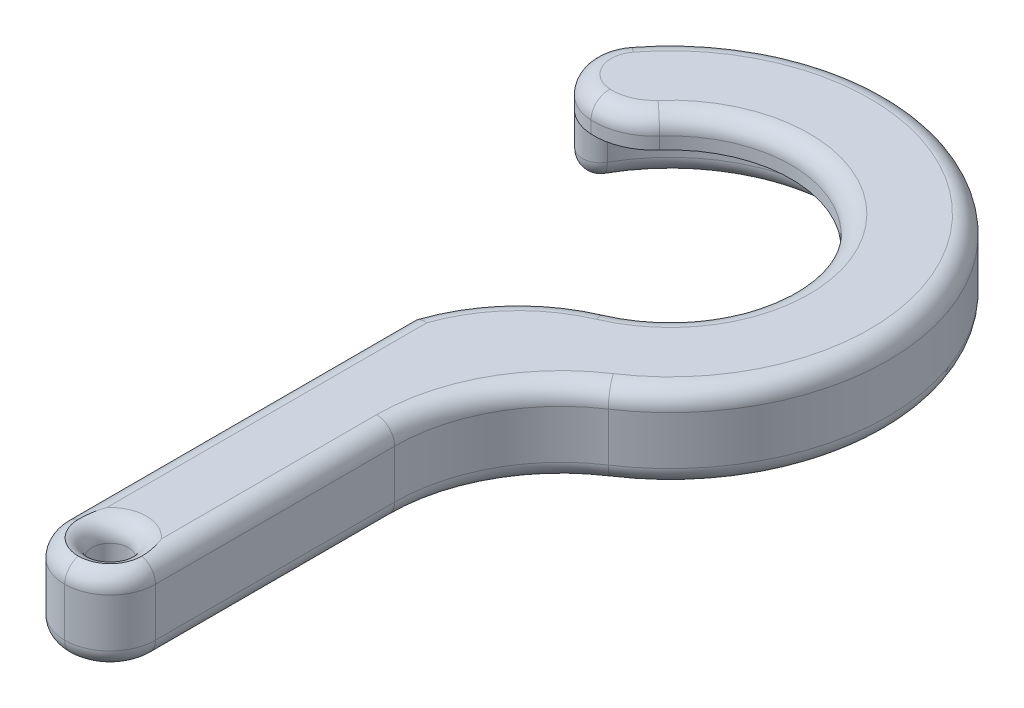
SolidWorks part; units mm, degrees
ref_plane "Front Plane" through (0, 0, 0) normal (0, 0, 1) x (1, 0, 0)
ref_plane "Top Plane" through (0, 0, 0) normal (0, 1, 0) x (1, 0, 0)
ref_plane "Right Plane" through (0, 0, 0) normal (1, 0, 0) x (0, 0, -1)
sketch "Sketch1" plane through (0, 0, 0) normal (0, 1, 0) x (1, 0, 0)
  circle A0 centre (0, 0) radius 6.858
  circle A1 centre (0, 0) radius 9.144
  dimension "D1" = 13.716
  dimension "D2" = 2.286
extrude "Boss-Extrude1" add sketch "Sketch1" along normal blind 2.286
sketch "Sketch2" plane through (0, 2.286, 0) normal (0, 1, 0) x (1, 0, 0)
  circle A0 centre (0, 0) radius 5.08
  circle M1 centre (0, 0) radius 9.144
  circle M2 centre (0, 0) radius 6.858
  dimension "D1" = 10.16
extrude "Boss-Extrude2" add sketch "Sketch2" along normal blind 1.27 contours A0 M2 | M1 M2
sketch "Sketch3" plane through (0, 3.556, 0) normal (0, 1, 0) x (1, 0, 0)
  line L0 (0, -1000) -> (0, 49000) construction
  line L1 (-1.905, -7.62) -> (1.905, -7.62)
  line L2 (-1.905, -7.62) -> (-1.905, -25.4)
  line L3 (-1.905, -25.4) -> (1.905, -25.4)
  line L4 (1.905, -7.62) -> (1.905, -25.4)
  dimension "D1" = 3.81
  dimension "D2" = 7.62
  dimension "D3" = 25.4
extrude "Boss-Extrude3" add sketch "Sketch3" against normal up to surface (3.556 mm away) up to face at (0, 0, 9.144)
sketch "Sketch4" plane through (0, 3.556, 0) normal (0, 1, 0) x (1, 0, 0)
  line L0 (-1.905, -8.9434) -> (0, 0)
  line L1 (0, 0) -> (-8.4767, 3.4291)
  arc A0 (1.905, -8.9434) -> (-1.905, -8.9434) centre (0, 0) ccw construction
  dimension "D1" = 100
extrude "Cut-Extrude1" cut sketch "Sketch4" against normal through all and the other way through all
fillet "Fillet1" radius 1.905 2 edges at (-1.905, 1.778, 25.4) (1.905, 1.778, 25.4)
sketch "Sketch5" plane through (0, 3.556, 0) normal (0, 1, 0) x (1, 0, 0)
  circle A0 centre (0, -23.495) radius 0.762
  arc A1 (-1.905, -23.495) -> (0, -25.4) centre (0, -23.495) ccw construction
  dimension "D1" = 1.524
extrude "Cut-Extrude2" cut sketch "Sketch5" against normal through all
fillet "Fillet2" radius 6.985 1 edges at (1.905, 1.778, 8.9434)
fillet "Fillet3" radius 6.985 1 edges at (-1.0583, 2.921, 4.9685)
fillet "Fillet4" radius 2.54 1 edges at (-4.7093, 2.921, -1.905)
fillet "Fillet5" radius 1.905 1 edges at (-8.4767, 1.778, -3.4291)
fillet "Fillet6" radius 0.762 2 edges at (-0.7789, 1.143, 6.8136) (-6.3427, 1.143, -2.6082)
fillet "Fillet7" radius 0.762 23 edges at (-1.5375, 0, 8.0323) (-0.7534, 0, 6.9262) (6.009, 0, -3.3052) (-6.5955, 0, -2.9638) (-7.6422, 0, -4.4213) (6.6945, 0, -6.2287) (2.7385, 0, 10.1489) (1.905, 0, 18.4764) (1.905, 3.556, 18.4764) (1.347, 0, 24.842) (-1.347, 0, 24.842) (-1.905, 0, 16.2192) (-1.905, 3.556, 16.2192) (-1.347, 3.556, 24.842) (1.347, 3.556, 24.842) (-0.4175, 3.556, 6.3846) (4.1192, 3.556, -2.973) (-4.7188, 3.556, -2.7091) (-7.4656, 3.556, -3.6134) (6.6945, 3.556, -6.2287) (0, 0, 24.257) (0, 3.556, 24.257) (2.7385, 3.556, 10.1489)
